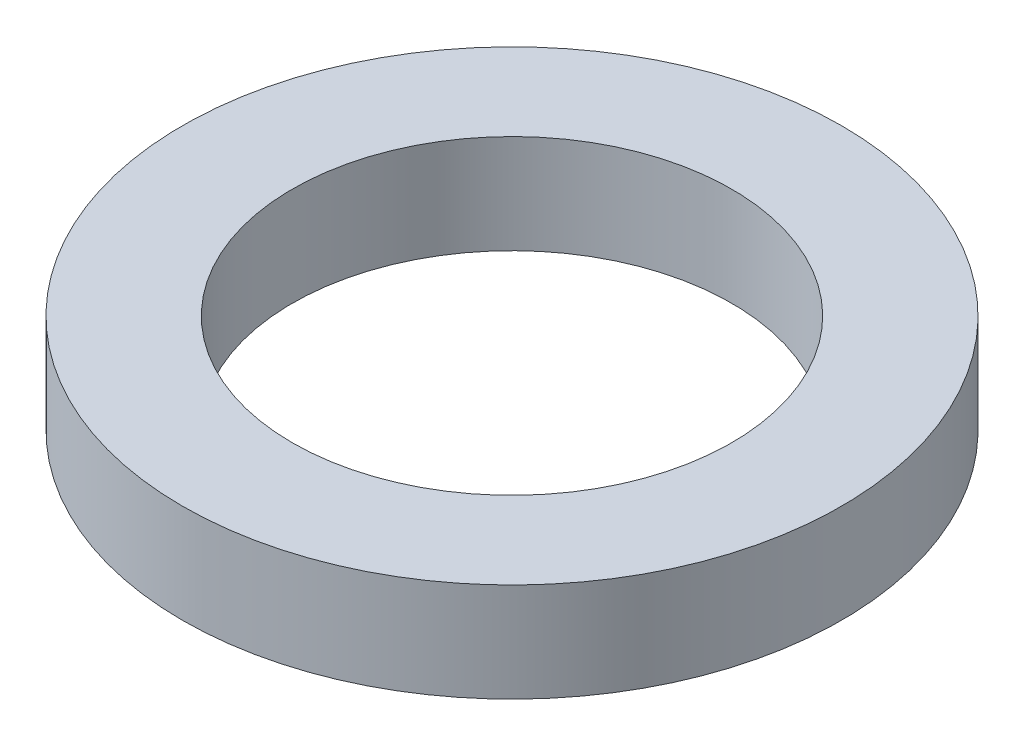
SolidWorks part; units mm, degrees
ref_plane "Front Plane" through (0, 0, 0) normal (0, 0, 1) x (1, 0, 0)
ref_plane "Top Plane" through (0, 0, 0) normal (0, 1, 0) x (1, 0, 0)
ref_plane "Right Plane" through (0, 0, 0) normal (1, 0, 0) x (0, 0, -1)
sketch "Sketch1" plane through (0, 0, 0) normal (0, 1, 0) x (1, 0, 0)
  circle A0 centre (0, 0) radius 30
  dimension "FLANGE_OD" = 60
extrude "Boss-Extrude1" add sketch "Sketch1" along normal blind 9
sketch "Sketch2" plane through (0, 0, 0) normal (0, 1, 0) x (1, 0, 0)
  circle A0 centre (0, 0) radius 20
  dimension "BORE_D" = 40
extrude "Cut-Extrude1" cut sketch "Sketch2" along normal through all
sketch "Sketch3" plane through (0, 9, 0) normal (0, 1, 0) x (1, 0, 0)
  circle A0 centre (0, 0) radius 11.5289 construction
  circle A1 centre (-11.5289, 0) radius 1.6269
  dimension "BOLT_D" = 3.2539
  dimension "BOLT_PCD" = 23.0578
extrude "Cut-Extrude2" cut sketch "Sketch3" against normal blind 6.0434 rebuild error yes
pattern_circular "CirPattern1" count 4 over 360 rebuild error yes
